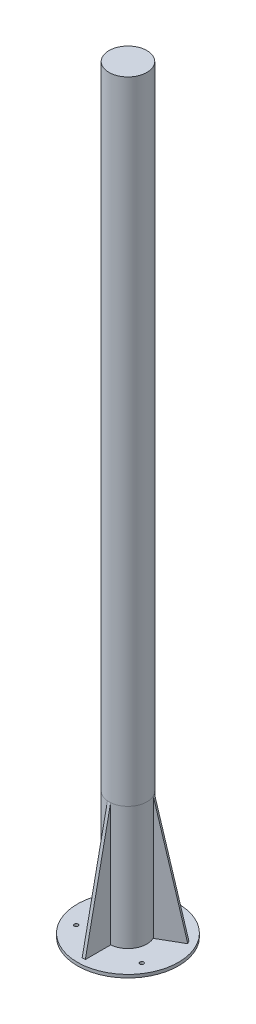
SolidWorks part; units mm, degrees
ref_plane "Front Plane" through (0, 0, 0) normal (0, 0, 1) x (1, 0, 0)
ref_plane "Top Plane" through (0, 0, 0) normal (0, 1, 0) x (1, 0, 0)
ref_plane "Right Plane" through (0, 0, 0) normal (1, 0, 0) x (0, 0, -1)
sketch "Sketch1" plane through (0, 0, 0) normal (0, 1, 0) x (1, 0, 0)
  circle A0 centre (0, 0) radius 80
  dimension "D1" = 160
extrude "Boss-Extrude1" add sketch "Sketch1" against normal blind 5
sketch "Sketch2" plane through (0, 0, 0) normal (0, 1, 0) x (1, 0, 0)
  circle A0 centre (0, 0) radius 30
  dimension "D1" = 60
extrude "Boss-Extrude2" add sketch "Sketch2" along normal blind 195
sketch "Sketch3" plane through (0, 0, 0) normal (1, 0, 0) x (0, 0, -1)
  line L0 (-70, 0) -> (-30, 0)
  line L1 (-30, 0) -> (-30, 195)
  line L2 (-30, 195) -> (-70, 0)
  line L3 (-30, 195) -> (-30, 0) construction
  line L4 (80, 0) -> (-80, 0) construction
  dimension "D1" = 40
  dimension "D2" = 195
  dimension "D3" = 0
  dimension "D4" = 0
extrude "Boss-Extrude3" add sketch "Sketch3" along normal blind 2.5 and the other way blind 2.5 separate body
pattern_circular "CirPattern5" count 3 every 120 about axis through (0, 195, 0) along (0, -1, 0) of bodies 103
sketch "Sketch4" plane through (0, 0, 0) normal (0, 1, 0) x (1, 0, 0)
  circle A0 centre (0, 60) radius 3
  circle A1 centre (0, 0) radius 30 construction
  circle A2 centre (51.9615, -30) radius 3
  circle A3 centre (-51.9615, -30) radius 3
  point P10 (0, 0)
  dimension "D1" = 6
  dimension "D2" = 60
  dimension "D3" = 3
extrude "Cut-Extrude1" cut sketch "Sketch4" against normal through all
sketch "Sketch5" plane through (0, 195, 0) normal (0, 1, 0) x (1, 0, 0)
  circle A0 centre (0, 0) radius 30 construction
  circle A1 centre (0, 0) radius 30
extrude "Boss-Extrude4" add sketch "Sketch5" along normal blind 1000 separate body
